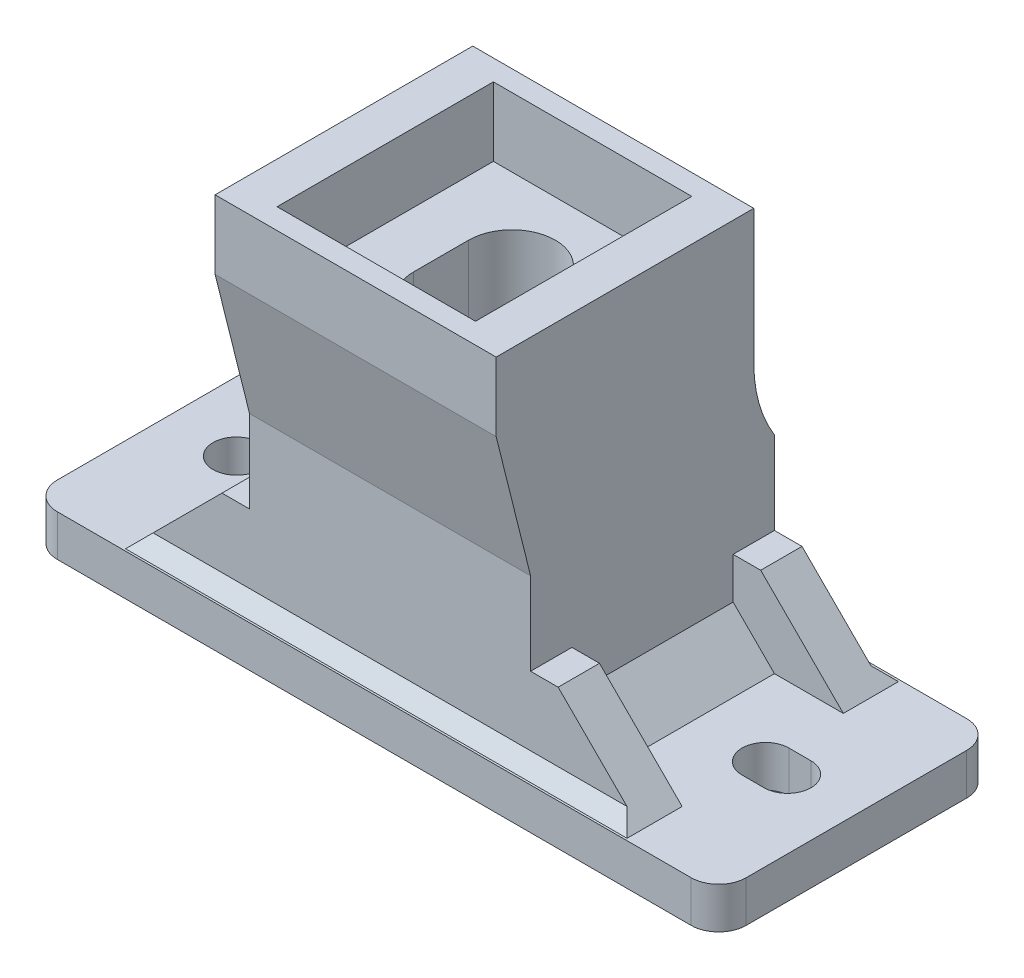
SolidWorks part; units mm, degrees
ref_plane "Front Plane" through (0, 0, 0) normal (0, 0, 1) x (1, 0, 0)
ref_plane "Top Plane" through (0, 0, 0) normal (0, 1, 0) x (1, 0, 0)
ref_plane "Right Plane" through (0, 0, 0) normal (1, 0, 0) x (0, 0, -1)
sketch "Sketch1" plane through (0, 0, 0) normal (0, 1, 0) x (1, 0, 0)
  line L1 (-7.2, -5.85) -> (7.2, -5.85)
  line L2 (-7.2, -5.85) -> (-7.2, 5.85)
  line L3 (-7.2, 5.85) -> (7.2, 5.85)
  line L4 (7.2, -5.85) -> (7.2, 5.85)
  line L5 (-7.2, -5.85) -> (7.2, 5.85) construction
  line L6 (-7.2, 5.85) -> (7.2, -5.85) construction
  line L7 (-10.2, -8.85) -> (10.2, -8.85)
  line L8 (-10.2, -8.85) -> (-10.2, 8.85)
  line L9 (-10.2, 8.85) -> (10.2, 8.85)
  line L10 (10.2, -8.85) -> (10.2, 8.85)
  line L11 (-10.2, -8.85) -> (10.2, 8.85) construction
  line L12 (-10.2, 8.85) -> (10.2, -8.85) construction
  circle A0 centre (0, 0) radius 3.15
  dimension "D1" = 6.3
  dimension "D2" = 11.7
  dimension "D3" = 14.4
  dimension "D4" = 3
  dimension "D5" = 3
extrude "Boss-Extrude1" add sketch "Sketch1" along normal blind 25 contours L7 L10 L9 L8 L4 L1 L2 L3 | L1 L4 L3 L2 A0 region at (-7.0145, 0, 0) region at (-9.9299, 0, 0)
extrude "Boss-Extrude2" add sketch "Sketch1<3>" along normal blind 30 contours L7 L10 L9 L8 L4 L1 L2 L3 region at (-9.9299, 0, 0)
sketch "Sketch1<3>" plane through (0, 0, 0) normal (0, 1, 0) x (1, 0, 0) same geometry as "Sketch1"
sketch "Sketch2" plane through (0, 30, 0) normal (0, 1, 0) x (1, 0, 0)
  line L0 (-10.2, 8.85) -> (10.2, 8.85) construction
  line L1 (-11.2249, 10.35) -> (11.2249, 10.35)
  line L2 (-11.2249, 10.35) -> (-11.2249, 7.35)
  line L3 (-11.2249, 7.35) -> (11.2249, 7.35)
  line L4 (11.2249, 10.35) -> (11.2249, 7.35)
  line L5 (-11.2249, 10.35) -> (11.2249, 7.35) construction
  line L6 (-11.2249, 7.35) -> (11.2249, 10.35) construction
  line L7 (7.2, 5.85) -> (-7.2, 5.85) construction
  point P0 (0, 8.85)
  dimension "D1" = 1.5
extrude "Cut-Extrude1" cut sketch "Sketch2" against normal blind 15
fillet "Fillet1" radius 10 1 edges at (0, 15, -7.35)
sketch "Sketch3" plane through (0, 0, 0) normal (0, -1, 0) x (1, 0, 0)
  line L1 (-25, -10) -> (25, -10)
  line L2 (-25, -10) -> (-25, 10)
  line L3 (-25, 10) -> (25, 10)
  line L4 (25, -10) -> (25, 10)
  line L5 (-25, -10) -> (25, 10) construction
  line L6 (-25, 10) -> (25, -10) construction
  circle A0 centre (0, 0) radius 3.15 construction
  circle A1 centre (0, 0) radius 3.15
  point P0 (0, 0)
  dimension "D1" = 50
  dimension "D2" = 20
extrude "Boss-Extrude3" add sketch "Sketch3" against normal blind 3
sketch "Sketch4" plane through (0, 3, 0) normal (0, 1, 0) x (1, 0, 0)
  line L0 (-25, 0) -> (25, 0) construction
  line L1 (-25, -10) -> (-25, 10) construction
  line L2 (25, 10) -> (25, -10) construction
  line L3 (-20, 0) -> (0, 10) construction
  line L4 (-25, 10) -> (25, 10) construction
  line L5 (0, 10) -> (20, 0) construction
  line L6 (18.4, 0) -> (20, 0) construction
  line L7 (18.4, 1.7) -> (20, 1.7)
  line L8 (18.4, -1.7) -> (20, -1.7)
  circle A0 centre (-20, 0) radius 1.7
  circle A1 centre (20, 0) radius 1.7 construction
  arc A2 (18.4, 1.7) -> (18.4, -1.7) centre (18.4, 0) ccw
  arc A3 (20, -1.7) -> (20, 1.7) centre (20, 0) ccw
  point P14 (19.2, 0)
  dimension "D1" = 3.4
  dimension "D4" = 5
  dimension "D2" = 5
  dimension "D3" = 40
extrude "Cut-Extrude2" cut sketch "Sketch4" against normal through all
sketch "Sketch5" plane through (0, 0, -8.85) normal (0, 0, -1) x (-1, 0, 0)
  line L0 (-10.2, 3) -> (-10.2, 9)
  line L1 (-10.2, 15) -> (-10.2, 3) construction
  line L2 (-10.2, 9) -> (-12.2, 9)
  line L3 (-12.2, 9) -> (-18.2, 3)
  line L4 (25, 3) -> (-25, 3) construction
  line L5 (-18.2, 3) -> (-10.2, 3)
  line L6 (0, 0) -> (0, 12.5638) construction
  line L7 (18.2, 3) -> (10.2, 3)
  line L8 (12.2, 9) -> (18.2, 3)
  line L9 (10.2, 9) -> (12.2, 9)
  line L10 (10.2, 3) -> (10.2, 9)
  dimension "D1" = 6
  dimension "D2" = 8
  dimension "D3" = 2
extrude "Boss-Extrude4" add sketch "Sketch5" against normal blind 3
sketch "Sketch6" plane through (0, 0, 8.85) normal (0, 0, 1) x (1, 0, 0)
  line L4 (-18.2, 3) -> (-10.2, 3)
  line L5 (-10.2, 3) -> (-10.2, 9)
  line L6 (-10.2, 9) -> (-12.2, 9)
  line L7 (-12.2, 9) -> (-18.2, 3)
  line L8 (-18.2, 3) -> (-10.2, 3)
  line L9 (-10.2, 3) -> (-10.2, 9)
  line L10 (-10.2, 9) -> (-12.2, 9)
  line L11 (-12.2, 9) -> (-18.2, 3)
  line L12 (10.2, 9) -> (10.2, 3)
  line L13 (12.2, 9) -> (10.2, 9)
  line L14 (18.2, 3) -> (12.2, 9)
  line L15 (10.2, 3) -> (18.2, 3)
  line L16 (10.2, 9) -> (10.2, 3)
  line L17 (12.2, 9) -> (10.2, 9)
  line L18 (18.2, 3) -> (12.2, 9)
  line L19 (10.2, 3) -> (18.2, 3)
  dimension "D1" = 0
  dimension "D2" = 0
extrude "Boss-Extrude5" add sketch "Sketch6" against normal blind 3
chamfer "Chamfer1" distance 3 angle 45 2 edges at (-10.2, 3, 0) (10.2, 3, 0)
chamfer "Chamfer2" distance 1 angle 45 2 edges at (0, 3, 8.85) (0, 3, -8.85)
fillet "Fillet3" radius 2 4 edges at (-25, 1.5, 10) (-25, 1.5, -10) (25, 1.5, 10) (25, 1.5, -10)
sketch "Sketch7" plane through (0, 30, 0) normal (0, 1, 0) x (1, 0, 0)
  line L1 (-7.2, -5.85) -> (7.2, -5.85)
  line L2 (-7.2, -5.85) -> (-7.2, -9.85)
  line L3 (-7.2, -9.85) -> (7.2, -9.85)
  line L4 (7.2, -5.85) -> (7.2, -9.85)
  line L5 (7.2, 5.85) -> (7.2, -5.85) construction
  line L6 (7.2, -5.85) -> (7.2, 5.85) construction
  line L7 (-10.2, -8.85) -> (-10.2, -11.35)
  line L8 (-17.2, -8.85) -> (17.2, -8.85) construction
  line L9 (-10.2, -8.85) -> (-10.2, 7.35) construction
  line L10 (-10.2, -11.35) -> (10.2, -11.35)
  line L11 (10.2, -11.35) -> (10.2, -5.85)
  line L12 (10.2, -5.85) -> (7.2, -5.85)
  line L13 (-10.2, -8.85) -> (-7.2, -8.85)
  line M7 (-10.2, -8.85) -> (10.2, -8.85)
  line M10 (7.2, -5.85) -> (-7.2, -5.85)
  dimension "D1" = 4
  dimension "D2" = 1.5
extrude "Cut-Extrude3" cut sketch "Sketch7" against normal up to surface (5 mm away) contours L4 L2 M10 M7 region at (0, 30, 7.35) up to face at (0, 25, 0)
extrude "Boss-Extrude6" add sketch "Sketch7<3>" against normal up to surface (5 mm away) contours L10 L11 L4 L3 L2 L7 M7 region at (0, 30, 10.3951) up to face at (0, 25, 1.5)
sketch "Sketch7<3>" plane through (0, 30, 0) normal (0, 1, 0) x (1, 0, 0) same geometry as "Sketch7"
sketch "Sketch8" plane through (0, 25, 0) normal (0, 1, 0) x (1, 0, 0)
  line L0 (0, 0) -> (0, -4) construction
  line L1 (3.15, 0) -> (3.15, -4)
  line L2 (-3.15, 0) -> (-3.15, -4)
  circle A0 centre (0, 0) radius 3.15 construction
  circle A1 centre (0, 0) radius 3.15 construction
  arc A2 (3.15, 0) -> (-3.15, 0) centre (0, 0) ccw
  arc A3 (-3.15, -4) -> (3.15, -4) centre (0, -4) ccw
  point P4 (0, -2)
  point P9 (0, 0)
  dimension "D1" = 4
extrude "Cut-Extrude4" cut sketch "Sketch8" against normal through all both and the other way through all
sketch "Sketch9" plane through (-10.2, 0, 0) normal (-1, 0, 0) x (0, 0, 1)
  line L0 (11.35, 25) -> (8.85, 25)
  line L1 (8.85, 25) -> (8.85, 15)
  line L2 (8.85, 15) -> (11.35, 25)
  dimension "D1" = 10
extrude "Boss-Extrude7" add sketch "Sketch9" against normal up to surface (20.4 mm away) up to face at (10.2, 16.0969, 0.6973)
